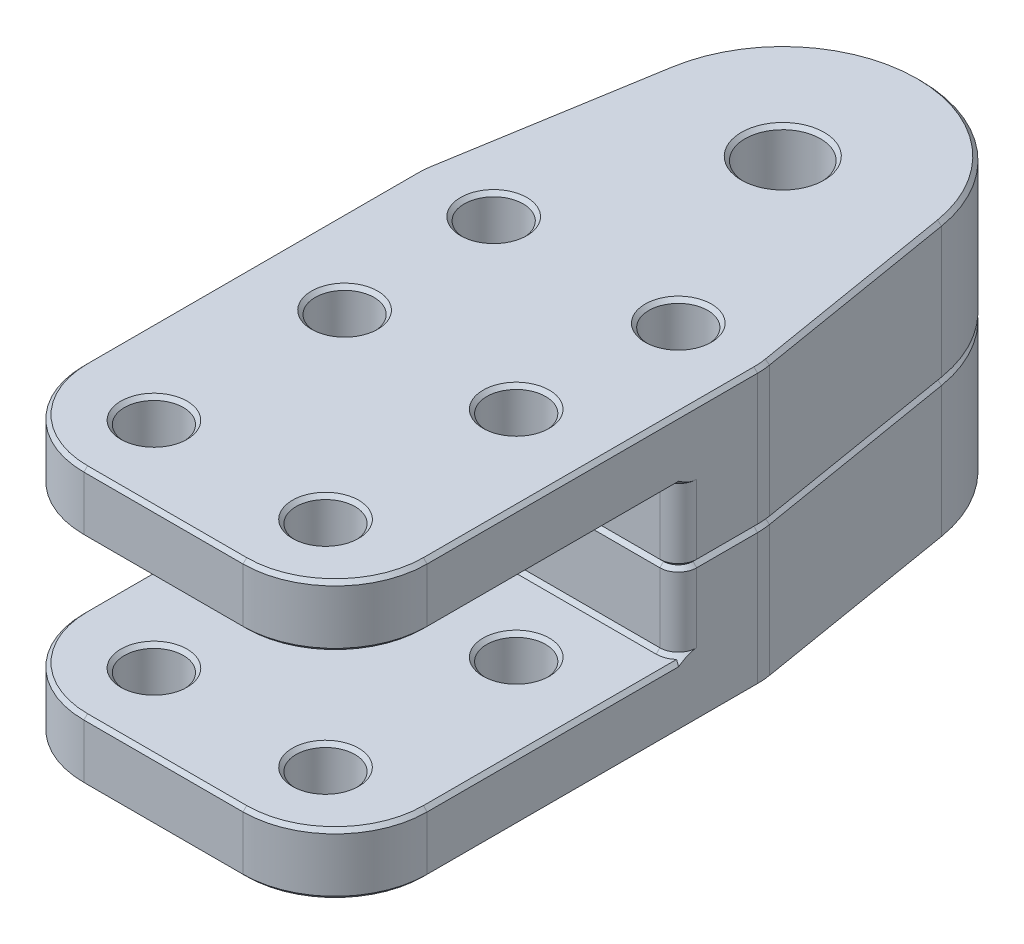
SolidWorks part; units mm, degrees
ref_plane "Front Plane" through (0, 0, 0) normal (1, 0, 0) x (0, 1, 0)
ref_plane "Top Plane" through (0, 0, 0) normal (0, 0, 1) x (0, 1, 0)
ref_plane "Right Plane" through (0, 0, 0) normal (0, 1, 0) x (-1, 0, 0)
sketch "Sketch1" plane through (0, 0, 0) normal (1, 0, 0) x (0, 1, 0)
  line L0 (-8.33, 37.29) -> (-15, 37.29)
  line L1 (0, 0) -> (-8.33, 0)
  line L2 (0, 0) -> (0, 37.29)
  line L3 (0, 37.29) -> (-8.33, 37.29)
  line L4 (-8.33, 0) -> (-8.33, 37.29)
  line L5 (-15, 37.29) -> (-15, -45)
  line L6 (-15, -45) -> (0, -45)
  line L7 (0, -45) -> (0, 0)
  dimension "D1" = 8.33
  dimension "D2" = 37.29
  dimension "D3" = 45
  dimension "D4" = 15
extrude "Boss-Extrude1" add sketch "Sketch1" against normal blind 37.29 contours L6 L7 L1 L4 L0 L5 region at (0, -8.6215, -11.4212)
sketch "Sketch2" plane through (0, -15, 0) normal (0, -1, 0) x (1, 0, 0)
  line L0 (-37.29, -45) -> (0, -45) construction
  line L1 (-18.645, -45) -> (-18.645, 37.29)
  line L2 (-37.1732, -10.0314) -> (-33.4416, -32.4616)
  line L3 (-27.9675, 37.29) -> (-27.9675, 0) construction
  line L4 (0, -45) -> (0, 37.29)
  line L5 (0, 37.29) -> (-37.29, 37.29)
  line L6 (-37.29, 37.29) -> (-37.29, -45)
  line L7 (-37.29, -45) -> (0, -45)
  line L8 (0, -45) -> (0, 37.29)
  line L9 (0, 37.29) -> (-37.29, 37.29)
  line L10 (-37.29, 37.29) -> (-37.29, -45)
  line L11 (-37.29, -45) -> (0, -45)
  line L12 (0, -45) -> (0, 0)
  line L13 (-37.29, -45) -> (0, -45)
  line L14 (-37.29, 0) -> (-37.29, -45)
  line L15 (0, 0) -> (-37.29, 0)
  line L16 (0, -45) -> (0, 0)
  line L17 (-37.29, -45) -> (0, -45)
  line L18 (-37.29, 0) -> (-37.29, -45)
  line L19 (0, 0) -> (-37.29, 0)
  line L20 (-37.29, 37.29) -> (-37.29, -45) construction
  line L21 (-0.1168, -10.0314) -> (-3.8484, -32.4616)
  line L22 (-9.3225, 37.29) -> (-9.3225, 0) construction
  circle A0 centre (-18.645, -30) radius 4.1
  circle A1 centre (-18.645, -30) radius 15
  circle A2 centre (-28.6727, -8.6173) radius 8.6173
  circle A3 centre (-28.6727, -8.6173) radius 3.2
  circle A4 centre (-8.6173, -8.6173) radius 8.6173
  circle A5 centre (-8.6173, -8.6173) radius 3.2
  circle A6 centre (-27.9675, 29.0033) radius 3.2
  circle A7 centre (-27.9675, 8.2867) radius 3.2
  circle A8 centre (-9.3225, 29.0033) radius 3.2
  circle A9 centre (-9.3225, 8.2867) radius 3.2
  point P11 (-18.645, -45)
  line M11 (0, -45) -> (0, 37.29)
  line M14 (-37.29, -45) -> (0, -45)
  dimension "D3" = 8.2
  dimension "D4" = 6.4
  dimension "D5" = 17.2346
  dimension "D8" = 6.4
  dimension "D12" = 30
  dimension "D6" = 18.645
  dimension "D7" = 9.3225
  dimension "D9" = 37.29
  dimension "D10" = 8.2867
  dimension "D11" = 8.2867
  dimension "D1" = 0
  dimension "D2" = 0
extrude "Cut-Extrude1" cut sketch "Sketch2" against normal through all contours A2 L18 A1 L2 M14 | A4 L21 A1 M11 M14 | A5 | L1 A0 | L1 A0 | A3 | A7 | A6 | A8 | A9 region at (-3.4519, -15, -35.2569) region at (-33.8381, -15, -35.2569) region at (-20.3851, -15, -30) region at (-16.9049, -15, -30) region at (-28.6727, -15, -8.6173) region at (-8.6173, -15, -8.6173) region at (-27.9675, -15, 29.0033) region at (-27.9675, -15, 8.2867) region at (-9.3225, -15, 29.0033) region at (-9.3225, -15, 8.2867)
fillet "Fillet1" radius 10 2 edges at (-37.29, -11.665, 37.29) (0, -11.665, 37.29)
fillet "Fillet2" radius 2 2 edges at (0, -4.165, 0) (-37.29, -4.165, 0)
chamfer "Chamfer1" distance 0.4 angle 45 34 edges at (-27.9675, -8.33, 11.4867) (-27.9675, -8.33, 32.2033) (-9.3225, -8.33, 32.2033) (-9.3225, -8.33, 11.4867) (-8.6173, -15, -11.8173) (-27.9675, -15, 5.0867) (-27.9675, -15, 25.8033) (-9.3225, -15, 25.8033) (-9.3225, -15, 5.0867) (-18.645, -15, -34.1) (-28.6727, -15, -11.8173) (-2.9289, -15, 34.3611) (0, -15, 9.3364) (-0.0293, -15, -9.3268) (-1.9826, -15, -21.2465) (-18.645, -15, -45) (-35.3074, -15, -21.2465) (-37.2607, -15, -9.3268) (-37.29, -15, 9.3364) (-34.3611, -15, 34.3611) (-18.645, -15, 37.29) (-36.7042, 0, -0.5858) (-37.29, 0, -5.3086) (-37.2607, 0, -9.3268) (-35.3074, 0, -21.2465) (-18.645, 0, -45) (-1.9826, 0, -21.2465) (-0.0293, 0, -9.3268) (0, 0, -5.3086) (-0.5858, 0, -0.5858) (-18.645, 0, 0) (-8.6173, 0, -11.8173) (-18.645, 0, -34.1) (-28.6727, 0, -11.8173)
chamfer "Chamfer2" distance 0.4 angle 45 3 edges at (-36.7042, -8.33, -0.5858) (-0.5858, -8.33, -0.5858) (-18.645, -8.33, 0)
chamfer "Chamfer3" distance 0.4 angle 45 5 edges at (-37.29, -8.33, 13.3083) (0, -8.33, 13.3083) (-34.3611, -8.33, 34.3611) (-2.9289, -8.33, 34.3611) (-18.645, -8.33, 37.29)
mirror "Mirror1" about plane through (-37.29, 0, 0) normal (0, 1, 0) of bodies 102
equation "\"D7@Sketch2\"=\"D6@Sketch2\"/2"
equation "\"D10@Sketch2\"=\"D9@Sketch2\"/4.5"
equation "\"D11@Sketch2\"=\"D10@Sketch2\""
